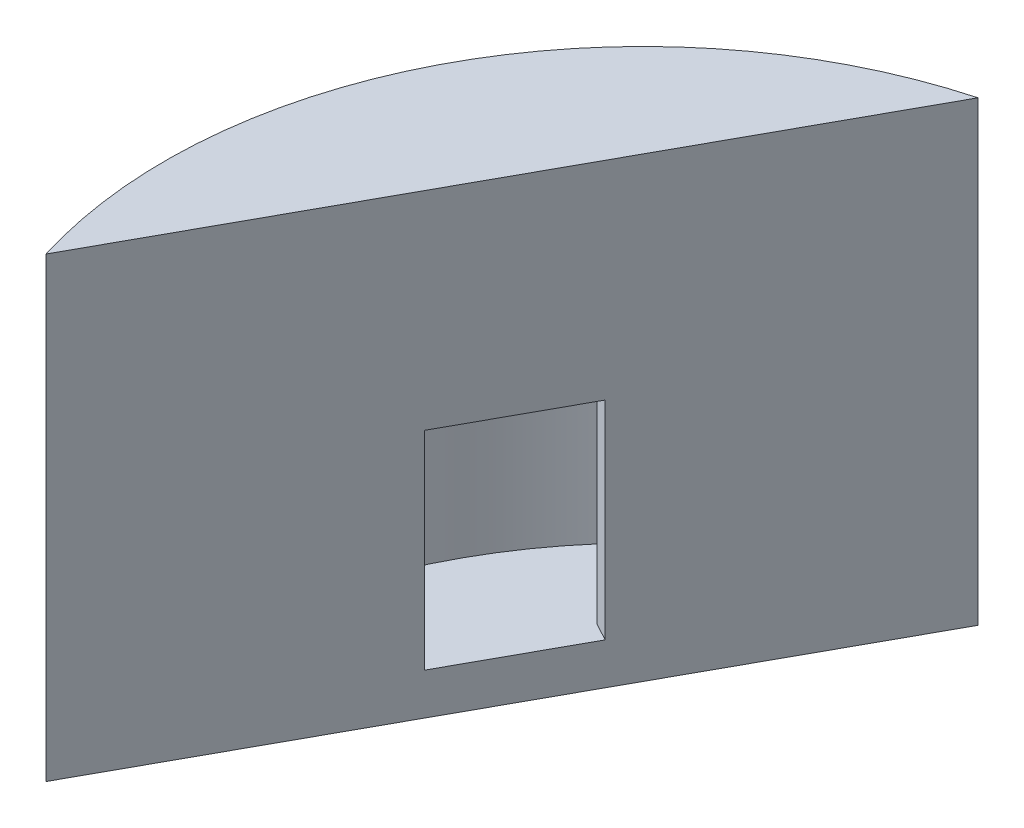
SolidWorks part; units mm, degrees
ref_plane "Front Plane" through (0, 0, 0) normal (0, 0, 1) x (1, 0, 0)
ref_plane "Top Plane" through (0, 0, 0) normal (0, 1, 0) x (1, 0, 0)
ref_plane "Right Plane" through (0, 0, 0) normal (1, 0, 0) x (0, 0, -1)
sketch "Sketch1" plane through (0, 0, 0) normal (0, 1, 0) x (1, 0, 0)
  circle A0 centre (0, 0) radius 69.85
  circle A1 centre (0, 0) radius 73.025
  dimension "D1" = 139.7
  dimension "D2" = 146.05
extrude "Boss-Extrude1" add sketch "Sketch1" along normal blind 63.5
sketch "Sketch2" plane through (0, 0, 0) normal (0, -1, 0) x (1, 0, 0)
  circle A0 centre (0, 0) radius 73.025
  dimension "D1" = 146.05
extrude "Boss-Extrude2" add sketch "Sketch2" along normal blind 6.35
sketch "Sketch3" plane through (0, 0, 0) normal (0, 1, 0) x (1, 0, 0)
  line L1 (-67.6153, -17.527) -> (-21.4092, 66.4881)
  circle A1 centre (0, 0) radius 69.85 construction
  arc A2 (-21.4092, 66.4881) -> (-67.6153, -17.527) centre (0, 0) ccw
  point P8 (0, 0)
  point P10 (-69.7753, -21.542)
  dimension "D1" = 50.8
extrude "Boss-Extrude3" add sketch "Sketch3" along normal blind 63.5
sketch "Sketch4" plane through (0, 63.5, 0) normal (0, 1, 0) x (1, 0, 0)
  line L0 (-25.7919, 64.9138) -> (-68.6329, -12.9827)
  line L1 (-67.6153, -17.527) -> (-21.4092, 66.4881) construction
  arc A0 (-25.7919, 64.9138) -> (-68.6329, -12.9827) centre (0, 0) ccw
  dimension "D2" = 69.85
  dimension "D1" = 88.9
extrude "Cut-Extrude2" cut sketch "Sketch4" against normal blind 57.15 from offset 6.35 offset against normal yes
ref_plane "Plane1" through (-42.2867, 0, -23.2565) normal (0.8762, 0, 0.4819) x (0.4819, 0, -0.8762)
sketch "Sketch6" plane through (-42.2867, 0, -23.2565) normal (0.8762, 0, 0.4819) x (0.4819, 0, -0.8762)
  line L0 (-47.9414, 0) -> (47.9414, 0) construction
  line L5 (-9.8414, 31.75) -> (10.4786, 31.75)
  line L6 (-9.8414, 31.75) -> (-9.8414, 0)
  line L7 (-9.8414, 0) -> (10.4786, 0)
  line L8 (10.4786, 31.75) -> (10.4786, 0)
  line L19 (-47.9414, 63.5) -> (-47.9414, 0) construction
  dimension "D1" = 38.1
  dimension "D2" = 31.75
  dimension "D6" = 20.32
extrude "Cut-Extrude4" cut sketch "Sketch6" against normal blind 31.75 from offset 19.05
sketch "Sketch7" plane through (0, 63.5, 0) normal (0, 1, 0) x (1, 0, 0)
  line L0 (-72.6096, -26.608) -> (-10.1714, 86.9215)
  line L1 (-10.1714, 86.9215) -> (114.9599, 65.8058)
  line L2 (114.9599, 65.8058) -> (122.5488, -33.7487)
  line L3 (122.5488, -33.7487) -> (41.0179, -93.9807)
  line L4 (41.0179, -93.9807) -> (-75.6034, -72.6768)
  line L5 (-75.6034, -72.6768) -> (-72.6096, -26.608)
  line L6 (-67.6153, -17.527) -> (-21.4092, 66.4881) construction
  point P8 (-70.9669, -27.2198)
  point P9 (41.0179, -93.9807)
extrude "Cut-Extrude5" cut sketch "Sketch7" against normal blind 1016
